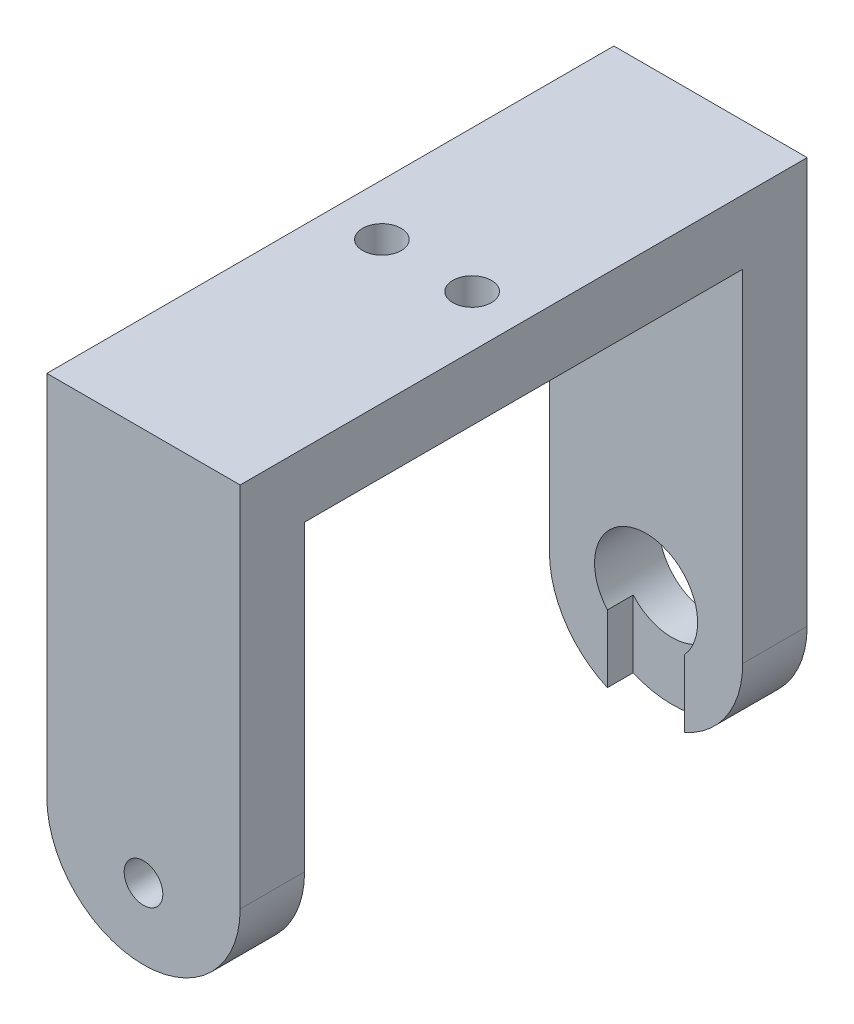
SolidWorks part; units mm, degrees
material "PET"
ref_plane "Alzado" through (0, 0, 0) normal (0, 0, 1) x (1, 0, 0)
ref_plane "Planta" through (0, 0, 0) normal (0, 1, 0) x (1, 0, 0)
ref_plane "Vista lateral" through (0, 0, 0) normal (1, 0, 0) x (0, 0, -1)
sketch "Croquis1" plane through (0, 0, 0) normal (0, 1, 0) x (1, 0, 0)
  line L1 (-7.5, -22) -> (7.5, -22)
  line L2 (-7.5, -22) -> (-7.5, 22)
  line L3 (-7.5, 22) -> (7.5, 22)
  line L4 (7.5, -22) -> (7.5, 22)
  line L5 (-7.5, -22) -> (7.5, 22) construction
  line L6 (-7.5, 22) -> (7.5, -22) construction
  circle A0 centre (3.5, 0) radius 1.5
  circle A1 centre (-3.5, 0) radius 1.5
  point P0 (0, 0)
  dimension "D3" = 3
  dimension "D4" = 4
  dimension "D5" = 7
  dimension "D1" = 15
  dimension "D2" = 44
extrude "Saliente-Extruir1" add sketch "Croquis1" against normal blind 5
sketch "Croquis2" plane through (0, -5, 0) normal (0, -1, 0) x (1, 0, 0)
  line L0 (7.5, 22) -> (7.5, -22) construction
  line L1 (-7.5, 22) -> (7.5, 22)
  line L2 (-7.5, 22) -> (-7.5, 17)
  line L3 (-7.5, 17) -> (7.5, 17)
  line L4 (7.5, 22) -> (7.5, 17)
  line L5 (-7.5, -22) -> (-7.5, 22) construction
  line L6 (7.5, -22) -> (-7.5, -22)
  line L7 (7.5, -22) -> (7.5, -17)
  line L8 (7.5, -17) -> (-7.5, -17)
  line L9 (-7.5, -22) -> (-7.5, -17)
  line M11 (7.5, -22) -> (7.5, 22)
  line M12 (7.5, 22) -> (-7.5, 22)
  line M13 (-7.5, 22) -> (-7.5, -22)
  dimension "D1" = 5
extrude "Saliente-Extruir2" add sketch "Croquis2" along normal blind 34 contours L7 L6 L9 L8
extrude "Saliente-Extruir3" add sketch "Croquis2<3>" along normal blind 31 contours L3 M13 M11 M12 region at (0, -5, 19.5)
sketch "Croquis2<3>" plane through (0, -5, 0) normal (0, -1, 0) x (1, 0, 0) same geometry as "Croquis2"
sketch "Croquis3" plane through (0, 0, 22) normal (0, 0, 1) x (1, 0, 0)
  line L0 (7.5, -36) -> (-7.5, -36) construction
  line L1 (-7.5, -28.5) -> (7.5, -28.5)
  circle A0 centre (0, -30.5) radius 1.5
  arc A1 (-7.5, -28.5) -> (7.5, -28.5) centre (0, -28.5) ccw
  line M5 (-7.5, 0) -> (-7.5, -36)
  line M6 (-7.5, -36) -> (7.5, -36)
  line M7 (7.5, -36) -> (7.5, 0)
  dimension "D1" = 3
  dimension "D3" = 15
  dimension "D2" = 5.5
  dimension "D4" = 7.5
extrude "Cortar-Extruir1" cut sketch "Croquis3" against normal up to next contours A0 | A1 M5 M6 | A1 M6 M7 region at (-5.8247, -34.3247, 22) region at (5.8247, -34.3247, 22) region at (0, -30.5, 22)
sketch "Croquis4" plane through (0, 0, -22) normal (0, 0, -1) x (-1, 0, 0)
  line L0 (-7.5, -39) -> (7.5, -39) construction
  circle A0 centre (0, -30.5) radius 4
  circle A1 centre (0, -31.5) radius 7.5
  line M4 (-7.5, 0) -> (-7.5, -39)
  line M5 (-7.5, -39) -> (7.5, -39)
  line M6 (7.5, -39) -> (7.5, 0)
  dimension "D1" = 8
  dimension "D3" = 15
  dimension "D2" = 8.5
  dimension "D4" = 7.5
extrude "Cortar-Extruir2" cut sketch "Croquis4" against normal up to next contours A0 | A1 M5 M6 | A1 M4 M5 region at (0, -30.5, -22) region at (-5.8247, -37.3247, -22) region at (5.8247, -37.3247, -22)
sketch "Croquis5" plane through (0, 0, -17) normal (0, 0, 1) x (1, 0, 0)
  line L0 (7.5, -5) -> (-7.5, -5) construction
  line L5 (-3, -33.1458) -> (3, -33.1458)
  line L6 (-3, -33.1458) -> (-3, -39)
  line L7 (-3, -39) -> (3, -39)
  line L8 (3, -33.1458) -> (3, -39)
  circle A0 centre (0, -30.5) radius 4 construction
  arc A1 (-7.5, -31.5) -> (7.5, -31.5) centre (0, -31.5) ccw construction
  point P6 (0, -5)
  point P7 (0, -33.1458)
  point P14 (0, -39)
  point P15 (0, -39)
  dimension "D1" = 6
extrude "Cortar-Extruir3" cut sketch "Croquis5" against normal blind 2
sketch "Croquis6" plane through (0, 0, -22) normal (0, 0, -1) x (-1, 0, 0)
  line L0 (7.5, -26.5) -> (-7.5, -26.5) construction
  line L1 (-3.4641, -10.5) -> (3.4641, -10.5)
  line L2 (-3.4641, -10.5) -> (-3.4641, -28.5)
  line L3 (-3.4641, -28.5) -> (3.4641, -28.5)
  line L4 (3.4641, -10.5) -> (3.4641, -28.5)
  line L5 (-7.5, -31.5) -> (-7.5, 0) construction
  line L6 (-2.125, -10.5) -> (-3.4641, -28.5)
  line L7 (2.125, -10.5) -> (3.4641, -28.5)
  line L8 (-2.125, -10.5) -> (2.125, -10.5) construction
  circle A0 centre (0, -30.5) radius 4 construction
  point P11 (0, -26.5)
  point P13 (0, -10.5)
  circle M6 centre (0, -30.5) radius 4
  dimension "D1" = 2
  dimension "D2" = 18
  dimension "D3" = 4.25
  dimension "D4" = 2.125
extrude "Cortar-Extruir4" cut sketch "Croquis6" against normal blind 3 contours L7 L1 L6 M6 region at (0, -19.4111, -22)
